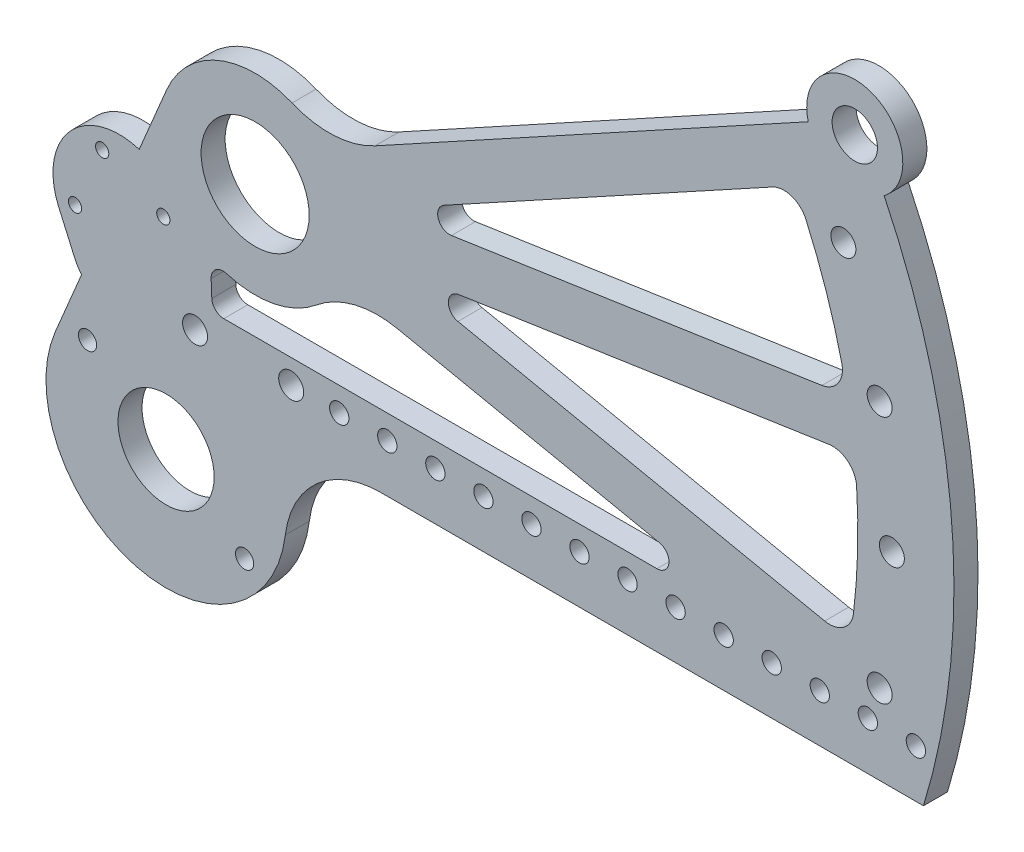
SolidWorks part; units mm, degrees
ref_plane "Front Plane" through (0, 0, 0) normal (0, 0, 1) x (1, 0, 0)
ref_plane "Top Plane" through (0, 0, 0) normal (0, 1, 0) x (1, 0, 0)
ref_plane "Right Plane" through (0, 0, 0) normal (1, 0, 0) x (0, 0, -1)
sketch "Model" plane through (0, 0, 0) normal (0, 0, 1) x (1, 0, 0)
  line L0 (51.8843, 14.181) -> (149.7957, 28.8257)
  line L1 (49.8885, 20.1052) -> (136.7019, 67.6925)
  line L2 (53.5879, -4.6282) -> (150.5258, -24.7317)
  line L3 (53.7629, 1.6207) -> (151.6743, 16.2654)
  line L4 (37.5401, -14.2704) -> (106.8353, -28.6411)
  line L5 (106.1906, -34.925) -> (-8.2841, -34.925)
  line L6 (0, 0) -> (165.0416, -32.8288) construction
  line L8 (176.627, -53.975) -> (33.1944, -53.975)
  line L9 (120.6444, 79.1079) -> (134.9495, 110.3615)
  line L10 (31.7217, 24.6299) -> (109.7579, 67.4058)
  line L11 (43.7839, 31.2418) -> (136.5177, 82.0744) construction
  line L14 (0, 0) -> (168.275, 0) construction
  line L15 (0, 0) -> (155.4658, 64.3961) construction
  line L16 (155.4658, 64.3961) -> (161.1052, 87.8857) construction
  line L17 (161.1052, 87.8857) -> (150.8624, 103.078) construction
  line L18 (150.8624, 103.078) -> (143.9681, 91.9613) construction
  line L19 (143.9681, 91.9613) -> (161.1052, 87.8857) construction
  line L20 (150.8624, 103.078) -> (163.3137, 101.9755) construction
  line L21 (150.8624, 103.078) -> (151.9649, 115.5293) construction
  line L22 (150.8624, 103.078) -> (138.4111, 104.1805) construction
  line L24 (49.8885, 20.1052) -> (142.6223, 70.9378) construction
  line L25 (171.5073, 71.1342) -> (168.2831, 104.749)
  line L26 (-49.0062, -42.6562) -> (184.69, -42.6562) construction
  line L27 (184.69, 0) -> (184.69, -42.6562) construction
  line L29 (-11.4566, -31.8747) -> (-11.6318, -27.4189)
  line L30 (0, 0) -> (165.0416, 32.8288) construction
  line L31 (0, 0) -> (-23.5374, -72.4737) construction
  line L32 (0, 0) -> (-54.9673, 52.7735) construction
  line L33 (0, 0) -> (24.5249, -72.1455) construction
  line L34 (-2.7815, -87.1145) -> (-44.2932, -57.8328) construction
  line L35 (-52.8124, -60.1841) -> (-23.42, 9.8317)
  arc A0 (49.8885, 20.1052) -> (51.8843, 14.181) centre (51.4146, 17.3211) ccw
  arc A1 (182.1934, -30.2649) -> (183.602, 20.017) centre (0, 0) ccw construction
  arc A2 (181.4238, 34.5801) -> (165.3645, 82.2494) centre (0, 0) ccw construction
  circle A4 centre (143.9681, 91.9613) radius 6.0008
  circle A5 centre (138.4111, 104.1805) radius 1.6
  circle A6 centre (161.1052, 87.8857) radius 6.0007
  circle A7 centre (150.8624, 103.078) radius 6.6
  circle A8 centre (151.9649, 115.5293) radius 1.6
  circle A9 centre (163.3137, 101.9755) radius 1.6
  arc A10 (-8.2841, -34.925) -> (-11.4566, -31.8747) centre (-8.2841, -31.75) cw
  arc A11 (-7.5193, -24.2615) -> (-11.6318, -27.4189) centre (-8.4593, -27.2942) ccw
  circle A13 centre (22.225, -41.275) radius 2.5527
  circle A14 centre (34.925, -41.275) radius 2.5527
  circle A15 centre (47.625, -41.275) radius 2.5527
  circle A16 centre (60.325, -41.275) radius 2.5527
  circle A17 centre (85.725, -41.275) radius 2.5527
  circle A18 centre (73.025, -41.275) radius 2.5527
  circle A19 centre (98.425, -41.275) radius 2.5527
  circle A20 centre (111.125, -41.275) radius 2.5527
  circle A21 centre (123.825, -41.275) radius 2.5527
  circle A22 centre (136.525, -41.275) radius 2.5527
  circle A23 centre (149.225, -41.275) radius 2.5527
  circle A24 centre (161.925, -41.275) radius 2.5527
  circle A25 centre (174.625, -41.275) radius 2.5527
  arc A27 (155.0368, 36.5634) -> (145.5567, 64.7035) centre (0, 0) ccw
  arc A28 (158.1185, -19.2827) -> (158.9501, 10.3998) centre (0, 0) ccw
  circle A31 centre (0, 0) radius 14.2811
  circle A32 centre (168.275, 0) radius 3.302
  circle A33 centre (155.4658, 64.3961) radius 3.302
  arc A34 (159.3837, -53.975) -> (144.6402, 85.9983) centre (0, 0) ccw construction
  arc A35 (53.7629, 1.6207) -> (53.5879, -4.6282) centre (54.2326, -1.5194) ccw
  arc A36 (157.1367, -26.1027) -> (158.3516, 17.2641) centre (0, 0) ccw construction
  arc A37 (158.1185, -19.2827) -> (150.5258, -24.7317) centre (151.8152, -18.514) cw
  arc A38 (158.9501, 10.3998) -> (151.6743, 16.2654) centre (152.6137, 9.9852) ccw
  arc A39 (-7.5193, -24.2615) -> (16.1911, -19.5706) centre (0, 0) ccw
  arc A40 (37.5401, -14.2704) -> (16.1911, -19.5706) centre (32.3822, -39.1412) ccw
  arc A41 (106.1906, -34.925) -> (106.8353, -28.6411) centre (106.1906, -31.75) ccw
  circle A42 centre (165.0416, -32.8288) radius 3.302
  circle A43 centre (165.0416, 32.8288) radius 3.302
  arc A47 (176.627, -53.975) -> (182.1934, -30.2649) centre (0, 0) ccw
  arc A48 (182.1934, -30.2649) -> (172.9991, 64.666) centre (0, 0) ccw
  arc A49 (156.473, 29.8244) -> (142.6223, 70.9378) centre (0, 0) ccw construction
  arc A50 (155.0368, 36.5634) -> (149.7957, 28.8257) centre (148.8564, 35.1058) cw
  arc A51 (9.7563, 23.4515) -> (31.7217, 24.6299) centre (19.5126, 46.9031) ccw
  arc A52 (9.7563, 23.4515) -> (-23.42, 9.8317) centre (0, 0) ccw
  arc A54 (145.5567, 64.7035) -> (136.7019, 67.6925) centre (139.7541, 62.1242) ccw
  arc A55 (168.2831, 104.749) -> (134.9495, 110.3615) centre (150.8624, 103.078) ccw
  arc A56 (159.9956, 88.1496) -> (160.6456, 88.5673) centre (150.8624, 103.078) ccw
  arc A57 (171.5073, 71.1342) -> (172.9991, 64.666) centre (196.7913, 73.5594) ccw
  arc A58 (120.6444, 79.1079) -> (109.7579, 67.4058) centre (97.5487, 89.6791) cw
  circle A59 centre (-15.875, -41.275) radius 3.302
  circle A60 centre (9.525, -41.275) radius 3.302
  arc A61 (-54.9673, 52.7735) -> (24.5249, -72.1455) centre (0, 0) ccw construction
  circle A62 centre (-23.5374, -72.4737) radius 12.7
  circle A63 centre (-23.5374, -72.4737) radius 25.4 construction
  circle A64 centre (-44.2932, -57.8328) radius 2.413
  circle A65 centre (-2.7815, -87.1145) radius 2.413
  arc A66 (-12.6295, -42.6562) -> (-12.8416, -42.5795) centre (-23.5374, -72.4737) ccw
  arc A67 (-52.8124, -60.1841) -> (7.9803, -76.3077) centre (-23.5374, -72.4737) ccw
  arc A68 (33.1944, -53.975) -> (7.9803, -76.3077) centre (33.1944, -79.375) ccw
  point P4 (155.2419, 74.0303)
  point P7 (168.3914, 34.9985)
  point P25 (-10.6073, -53.4761)
  point P27 (-12.6902, -0.4989)
  dimension "D2" = 28.5623
  dimension "D3" = 25.4
  dimension "D15" = 35.0012
  dimension "D16" = 25.4
  dimension "D17" = 6.35
  dimension "D18" = 6.604
  dimension "D19" = 6.604
  dimension "D20" = 3.175
  dimension "D21" = 25.4
  dimension "D22" = 11.25
  dimension "D23" = 6.604
  dimension "D24" = 6.604
  dimension "D25" = 6.604
  dimension "D27" = 6.604
  dimension "D29" = 152.4
  dimension "D28" = 25.4
  dimension "D30" = 50.8
  dimension "D31" = 4.826
  dimension "D32" = 4.826
  dimension "D33" = 63.5
  dimension "D1" = 168.275
  dimension "D4" = 12.7
  dimension "D5" = 168.275
  dimension "D6" = 126
  dimension "D7" = 24.1571
  dimension "D8" = 17.615
  dimension "D9" = 18.3227
  dimension "D10" = 13.081
  dimension "D11" = 12.5
  dimension "D12" = 12.5
  dimension "D13" = 12.5
  dimension "D26" = 11.25
  dimension "D14" = 25.4
extrude "Boss-Extrude2" add sketch "Model" along normal blind 6.35 contours L9 A58 L10 A51 A52 L8 A47 A48 A57 L25 A55 A4 A5 A6 A7 A8 A9 A13 A14 A15 A16 A17 A18 A19 A20 region at (104.9107, -50.6868, 0)
sketch "Sketch2" plane through (0, 0, 6.35) normal (0, 0, 1) x (1, 0, 0)
  line L0 (109.7579, 67.4058) -> (143.625, 85.9703)
  line L2 (171.5073, 71.1342) -> (168.2831, 104.749) construction
  line L3 (120.6444, 79.1079) -> (134.9495, 110.3615) construction
  line L4 (171.5073, 71.1342) -> (168.2831, 104.749)
  line L5 (120.6444, 79.1079) -> (134.9495, 110.3615)
  line L6 (149.2031, 89.028) -> (158.8062, 94.292)
  line L7 (143.625, 85.9703) -> (149.2031, 89.028)
  arc A0 (172.9991, 64.666) -> (159.2244, 93.5841) centre (0, 0) ccw
  arc A1 (171.5073, 71.1342) -> (172.9991, 64.666) centre (196.7913, 73.5594) ccw construction
  arc A2 (168.2831, 104.749) -> (134.9495, 110.3615) centre (150.8624, 103.078) ccw construction
  arc A3 (109.7579, 67.4058) -> (120.6444, 79.1079) centre (97.5487, 89.6791) ccw construction
  arc A4 (171.5073, 71.1342) -> (172.9991, 64.666) centre (196.7913, 73.5594) ccw
  arc A5 (168.2831, 104.749) -> (134.9495, 110.3615) centre (150.8624, 103.078) ccw
  arc A6 (109.7579, 67.4058) -> (120.6444, 79.1079) centre (97.5487, 89.6791) ccw
  circle A7 centre (161.1052, 87.8857) radius 6.0007 construction
  circle A9 centre (143.9681, 91.9613) radius 6.0008 construction
  arc A10 (159.2244, 93.5841) -> (164.8784, 83.2196) centre (161.1052, 87.8857) ccw
  arc A11 (143.625, 85.9703) -> (149.2031, 89.028) centre (143.9681, 91.9613) ccw
  arc A12 (159.2244, 93.5841) -> (158.8062, 94.292) centre (0, 0) ccw
extrude "Boss-Extrude3" add sketch "Sketch2" against normal through all contours L7 A11 | A0 A10 region at (146.5907, 87.177, 6.35) region at (159.3999, 86.9554, 6.35)
extrude "Cut-Extrude2" cut sketch "Sketch2<3>" against normal through all contours A12 A0 A4 L4 A5 L5 A6 L0 L7 L6 region at (147.318, 98.3456, 6.35)
sketch "Sketch2<3>" plane through (0, 0, 6.35) normal (0, 0, 1) x (1, 0, 0) same geometry as "Sketch2"
sketch "Sketch3" plane through (0, 0, 0) normal (0, 0, -1) x (-1, 0, 0)
  line L1 (47.5699, -41.0132) -> (51.9346, -31.1397)
  line L4 (52.8124, -60.1841) -> (23.42, 9.8317) construction
  line L5 (45.8592, -43.6206) -> (30.6457, -7.3807)
  circle A0 centre (40.4212, -12.3994) radius 1.75
  circle A1 centre (24.2639, -19.5717) radius 1.75
  circle A2 centre (47.5935, -28.5567) radius 1.75
  arc A5 (47.5699, -41.0132) -> (45.8592, -43.6206) centre (38.8582, -37.1622) cw
  arc A6 (30.6457, -7.3807) -> (51.9346, -31.1397) centre (35.9287, -24.0642) cw
extrude "Boss-Extrude4" add sketch "Sketch3" against normal through all contours A0 | A2 | L1 A6 L5 A5 region at (-40.4212, -12.3994, 0) region at (-47.5935, -28.5567, 0)
extrude "Cut-Extrude3" cut sketch "Sketch3<6>" against normal through all contours A1
sketch "Sketch3<6>" plane through (0, 0, 0) normal (0, 0, -1) x (-1, 0, 0) same geometry as "Sketch3"
sketch "Sketch8" plane through (0, 0, 0) normal (0, 0, -1) x (-1, 0, 0)
  line L0 (-158.8062, 94.292) -> (-146.1701, 87.3654)
  line L1 (-31.7217, 24.6299) -> (-158.8062, 94.292) construction
  arc A1 (-146.1701, 87.3654) -> (-166.2421, 80.4608) centre (-158.4749, 90.5087) ccw
  arc A2 (-158.8062, 94.292) -> (-166.2421, 80.4608) centre (0, 0) ccw
  arc A3 (-158.8062, 94.292) -> (-176.627, -53.975) centre (0, 0) ccw construction
  dimension "D2" = 25.4
extrude "Boss-Extrude5" add sketch "Sketch8" against normal through all
sketch "Sketch9" plane through (0, 0, 0) normal (0, 0, -1) x (-1, 0, 0)
  circle A0 centre (-158.4749, 90.5087) radius 5.9944
  dimension "D1" = 11.9888
extrude "Cut-Extrude4" cut sketch "Sketch9" against normal through all
